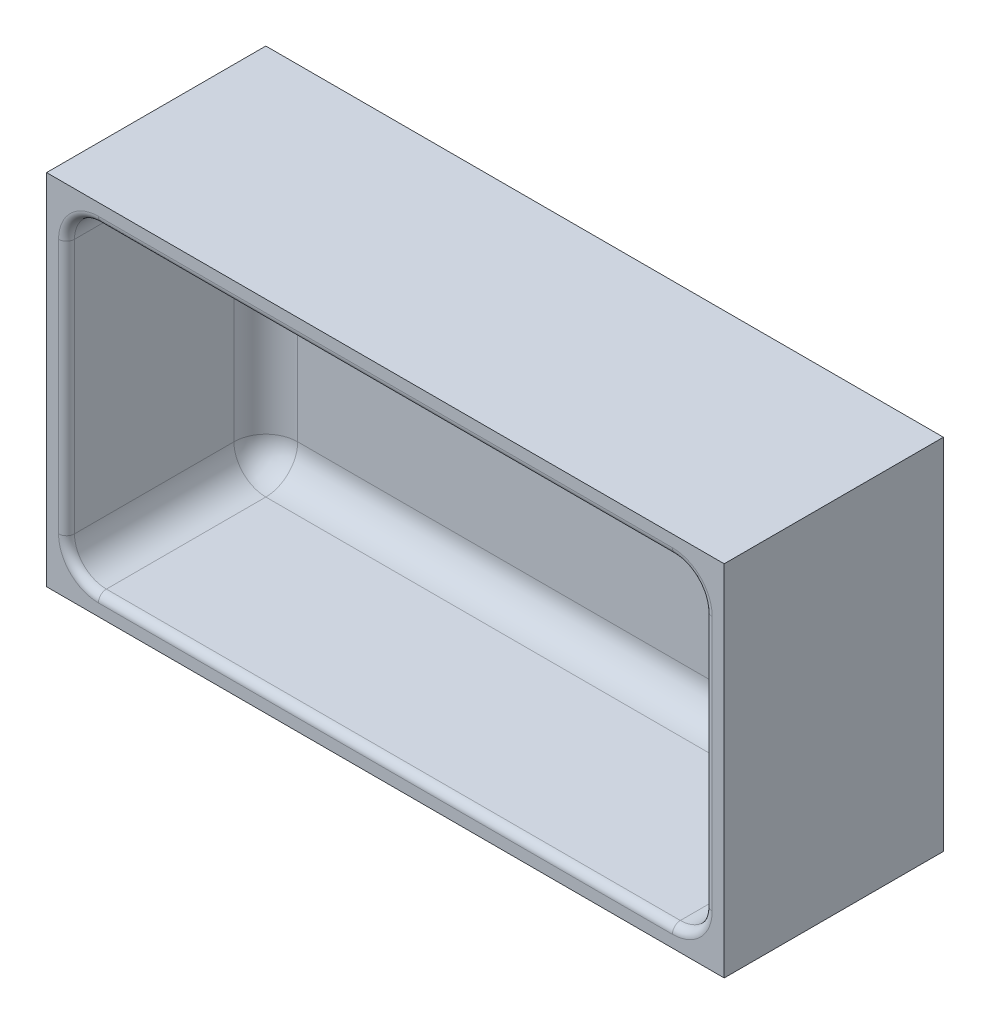
SolidWorks part; units mm, degrees
ref_plane "Ön Düzlem" through (0, 0, 0) normal (1, 0, 0) x (0, 1, 0)
ref_plane "Üst Düzlem" through (0, 0, 0) normal (0, 0, 1) x (0, 1, 0)
ref_plane "Sağ Düzlem" through (0, 0, 0) normal (0, 1, 0) x (-1, 0, 0)
sketch "Çizim1" plane through (0, 0, 0) normal (0, 0, 1) x (0, 1, 0)
  line L0 (0, 0) -> (90, 0)
  line L1 (0, 0) -> (0, 170)
  line L2 (0, 170) -> (90, 170)
  line L3 (90, 170) -> (90, 0)
  line L4 (5, 5) -> (5, 165)
  line L5 (5, 165) -> (85, 165)
  line L6 (85, 165) -> (85, 5)
  line L7 (5, 5) -> (85, 5)
  dimension "D1" = 5
extrude "Yükseklik-Ekstrüzyon1" add sketch "Çizim1" along normal blind 5 contours L4 L5 L6 L7
extrude "Yükseklik-Ekstrüzyon2" add sketch "Çizim1<3>" along normal blind 55
sketch "Çizim1<3>" plane through (0, 0, 0) normal (0, 0, 1) x (0, 1, 0) same geometry as "Çizim1"
fillet "Radyus2" radius 8 8 edges at (-5, 5, 30) (-5, 85, 30) (-165, 85, 30) (-165, 5, 30) (-5, 45, 5) (-85, 5, 5) (-85, 85, 5) (-165, 45, 5)
fillet "Radyus4" radius 2 8 edges at (-162.6569, 82.6569, 55) (-7.3431, 82.6569, 55) (-7.3431, 7.3431, 55) (-162.6569, 7.3431, 55) (-85, 85, 55) (-5, 45, 55) (-85, 5, 55) (-165, 45, 55)
